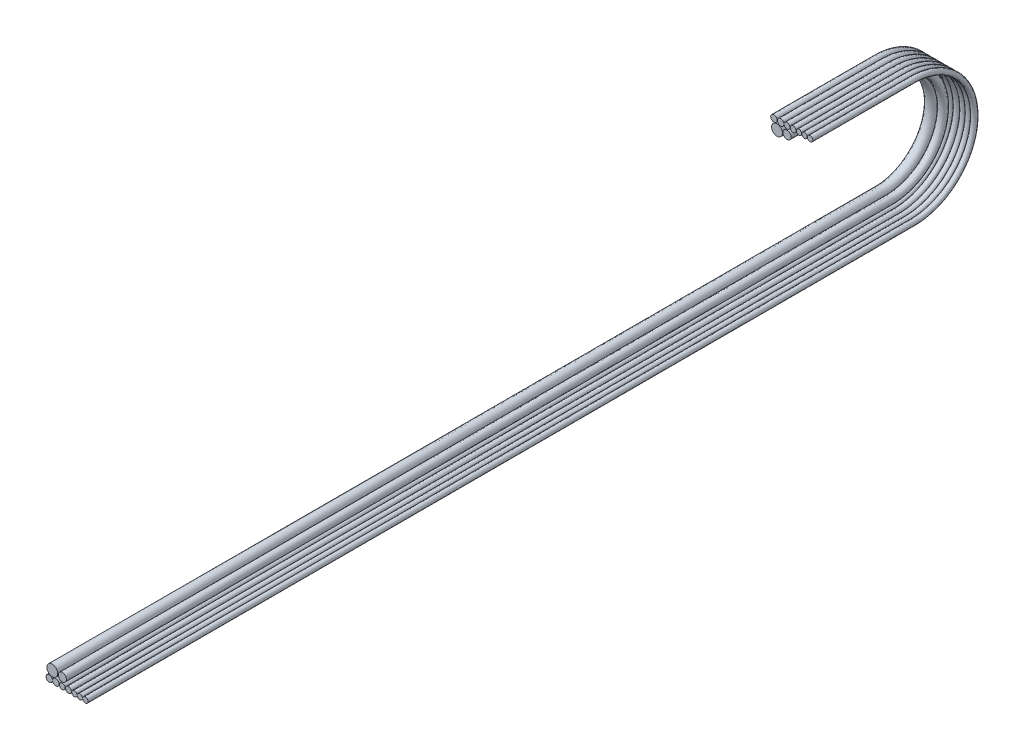
SolidWorks part; units mm, degrees
ref_plane "Front Plane" through (0, 0, 0) normal (0, 0, 1) x (1, 0, 0)
ref_plane "Top Plane" through (0, 0, 0) normal (0, 1, 0) x (1, 0, 0)
ref_plane "Right Plane" through (0, 0, 0) normal (1, 0, 0) x (0, 0, -1)
sketch "Sketch1" plane through (0, 0, 0) normal (0, 0, 1) x (1, 0, 0)
  line L1 (18.5, 18) -> (-18.5, 18) construction
  line L2 (18.5, 18) -> (18.5, 0) construction
  line L3 (18.5, 0) -> (-18.5, 0) construction
  line L4 (-18.5, 18) -> (-18.5, 0) construction
  circle A0 centre (-16.1, 2.4) radius 2.4
  circle A1 centre (-11.18, 2.4) radius 2.4
  circle A2 centre (-6.4473, 2.15) radius 2.15
  circle A3 centre (-1.9096, 2.15) radius 2.15
  circle A4 centre (2.4561, 1.95) radius 1.95
  circle A5 centre (6.4782, 1.95) radius 1.95
  circle A6 centre (10.6033, 2) radius 2
  circle A7 centre (-13.8535, 8.6823) radius 4
  circle A8 centre (-6.4473, 8.0498) radius 3
  dimension "D3" = 4.8
  dimension "D4" = 4.3
  dimension "D5" = 3.9
  dimension "D6" = 4
  dimension "D7" = 8
  dimension "D8" = 6
  dimension "D1" = 37
  dimension "D2" = 18
sketch "Sketch2" plane through (0, 0, 0) normal (1, 0, 0) x (0, 0, -1)
  spline S0 degree 3 poles (-999.998, 9.7) (-462.9788, 9.7) (74.1125, 9.7) (611.2757, 9.7) (611.4917, 9.7023) (611.6357, 9.7043) (611.7076, 9.7055) (684.6997, 10.9502) (684.9458, 83.9525) (611.9638, 85.6892) (611.8633, 85.6916) (611.6625, 85.6956) (611.3611, 85.7) (252.6429, 85.7) (-105.9749, 85.7) (-464.4922, 85.7) knots -1.308631 -1.308631 -1.308631 -1.308631 0.799653 0.799936 0.800219 0.800501 0.800501 0.800501 0.899937 0.899937 0.899937 0.900331 0.900726 0.90112 2.308624 2.308624 2.308624 2.308624 weights 1 1 1 1 1 1 1 0.346947 0.346947 1 1 1 1 1 1 1 only from (0, 9.7) to (535.5, 85.7) construction
  spline S1 degree 3 poles (0, 9.7) (203.6866, 9.7) (407.4452, 9.7) (611.2757, 9.7) (611.4917, 9.7023) (611.6357, 9.7043) (611.7076, 9.7055) (684.6997, 10.9502) (684.9458, 83.9525) (611.9638, 85.6892) (611.8633, 85.6916) (611.6625, 85.6956) (611.3611, 85.7) (585.9736, 85.7) (560.6866, 85.7) (535.5, 85.7) knots 0 0 0 0 0.799653 0.799936 0.800219 0.800501 0.800501 0.800501 0.899937 0.899937 0.899937 0.900331 0.900726 0.90112 1 1 1 1 weights 1 1 1 1 1 1 1 0.346947 0.346947 1 1 1 1 1 1 1
sweep "Sweep1" add profiles "Sketch1" path "Sketch2"
